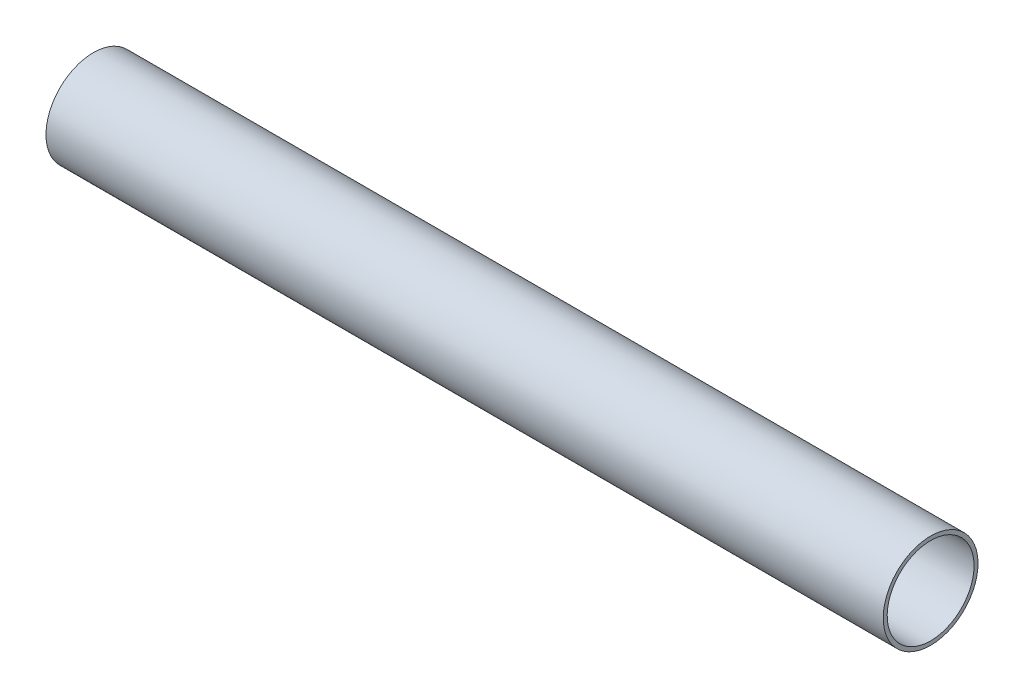
SolidWorks part; units mm, degrees
material "Hexcel AS4C (3000 Filaments)"
ref_plane "Front Plane" through (0, 0, 0) normal (0, 0, 1) x (1, 0, 0)
ref_plane "Top Plane" through (0, 0, 0) normal (0, 1, 0) x (1, 0, 0)
ref_plane "Right Plane" through (0, 0, 0) normal (1, 0, 0) x (0, 0, -1)
sketch "Sketch1" plane through (-15.5279, 0, 0) normal (-1, 0, 0) x (0, 0, 1)
  circle A1 centre (50, 105.8696) radius 11
  circle A2 centre (50, 105.8696) radius 12
  dimension "D2" = 22
  dimension "D1" = 1
extrude "Boss-Extrude1" add sketch "Sketch1" against normal mid plane 212
equation "\"inner_fuselage_width\"=212"
equation "\"D1@Boss-Extrude1\"=\"inner_fuselage_width\""
